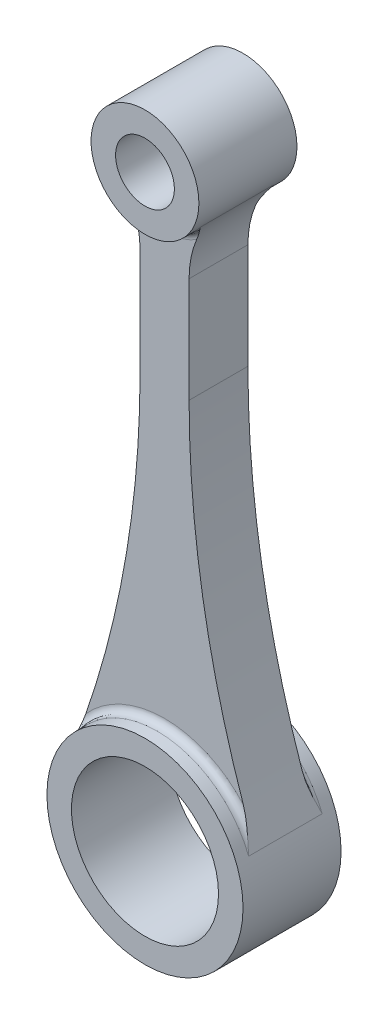
SolidWorks part; units mm, degrees
ref_plane "Płaszczyzna przednia" through (0, 0, 0) normal (0, 0, 1) x (1, 0, 0)
ref_plane "Płaszczyzna górna" through (0, 0, 0) normal (0, 1, 0) x (1, 0, 0)
ref_plane "Płaszczyzna prawa" through (0, 0, 0) normal (1, 0, 0) x (0, 0, -1)
sketch "Szkic1" plane through (0, 0, 0) normal (0, 0, 1) x (1, 0, 0)
  circle A0 centre (0, 0) radius 20
  circle A1 centre (0, 0) radius 15
  circle A2 centre (0, 120) radius 6
  circle A3 centre (0, 120) radius 11
  dimension "D1" = 40
  dimension "D2" = 30
  dimension "D4" = 12
  dimension "D5" = 22
  dimension "D3" = 120
extrude "Dodanie-wyciągnięcie1" add sketch "Szkic1" along normal mid plane 20
sketch "Szkic2" plane through (0, 0, 0) normal (0, 0, 1) x (1, 0, 0)
  line L0 (5, 110.202) -> (5, 80.202)
  line L1 (-5, 110.202) -> (-5, 80.202)
  line L2 (0, 121.638) -> (0, 0) construction
  arc A0 (5, 80.202) -> (18.6481, 7.2283) centre (206.9122, 80.202) ccw
  circle A2 centre (0, 120) radius 11 construction
  circle A3 centre (0, 0) radius 20 construction
  arc A4 (-5, 80.202) -> (-18.6481, 7.2283) centre (-206.9122, 80.202) cw
  arc A5 (-5, 110.202) -> (5, 110.202) centre (0, 120) ccw
  arc A6 (18.6481, 7.2283) -> (-18.6481, 7.2283) centre (0, 0) ccw
  dimension "D1" = 30
  dimension "D2" = 5
extrude "Dodanie-wyciągnięcie2" add sketch "Szkic2" along normal mid plane 12
fillet "Zaokrąglenie1" radius 1.5 4 edges at (0, 109, 6) (0, 109, -6) (0, 20, -6) (0, 20, 6)
fillet "Zaokrąglenie2" radius 20 2 edges at (-5, 110.202, 0) (5, 110.202, 0)
